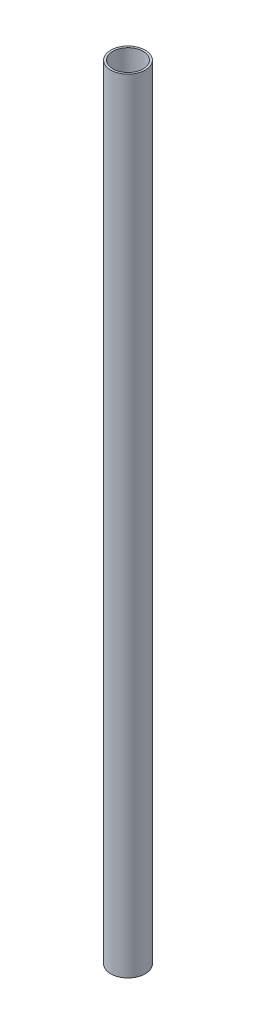
SolidWorks part; units mm, degrees
ref_plane "Front Plane" through (0, 0, 0) normal (0, 0, 1) x (1, 0, 0)
ref_plane "Top Plane" through (0, 0, 0) normal (0, 1, 0) x (1, 0, 0)
ref_plane "Right Plane" through (0, 0, 0) normal (1, 0, 0) x (0, 0, -1)
sketch "Sketch1" plane through (0, 0, 0) normal (0, 1, 0) x (1, 0, 0)
  circle A0 centre (0, 0) radius 7.8994
  circle A1 centre (0, 0) radius 8.9662
extrude "Boss-Extrude1" add sketch "Sketch1" along normal blind 406.4
